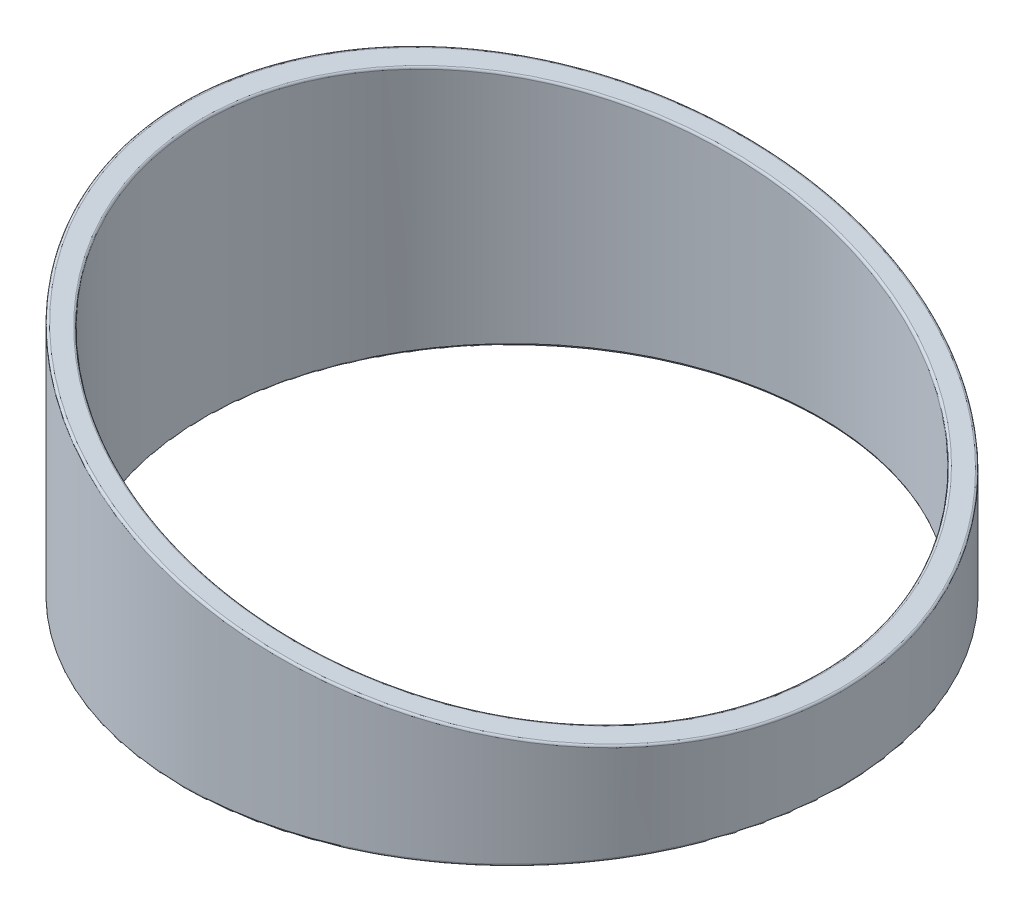
SolidWorks part; units mm, degrees
ref_plane "Front Plane" through (0, 0, 0) normal (0, 0, 1) x (1, 0, 0)
ref_plane "Top Plane" through (0, 0, 0) normal (0, 1, 0) x (1, 0, 0)
ref_plane "Right Plane" through (0, 0, 0) normal (1, 0, 0) x (0, 0, -1)
sketch "Sketch1" plane through (0, 0, 0) normal (0, 1, 0) x (1, 0, 0)
  circle A0 centre (0, 0) radius 29
  circle A1 centre (0, 0) radius 31
  dimension "D1" = 58
  dimension "D2" = 2
extrude "Boss-Extrude1" add sketch "Sketch1" along normal blind 25
sketch "Sketch2" plane through (0, 0, 0) normal (0, 0, 1) x (1, 0, 0)
  line L0 (-31, 25) -> (31, 8)
  line L1 (31, 0) -> (31, 25) construction
  line L2 (31, 8) -> (31, 25)
  line L3 (31, 25) -> (-31, 25)
  line L4 (-31, 0) -> (31, 0) construction
  dimension "D1" = 8
extrude "Cut-Extrude1" cut sketch "Sketch2" against normal through all both and the other way through all
fillet "Fillet1" radius 0.2 4 edges at (31, 8, 0) (29, 8.5484, 0) (0, 0, 29) (0, 0, 31)
